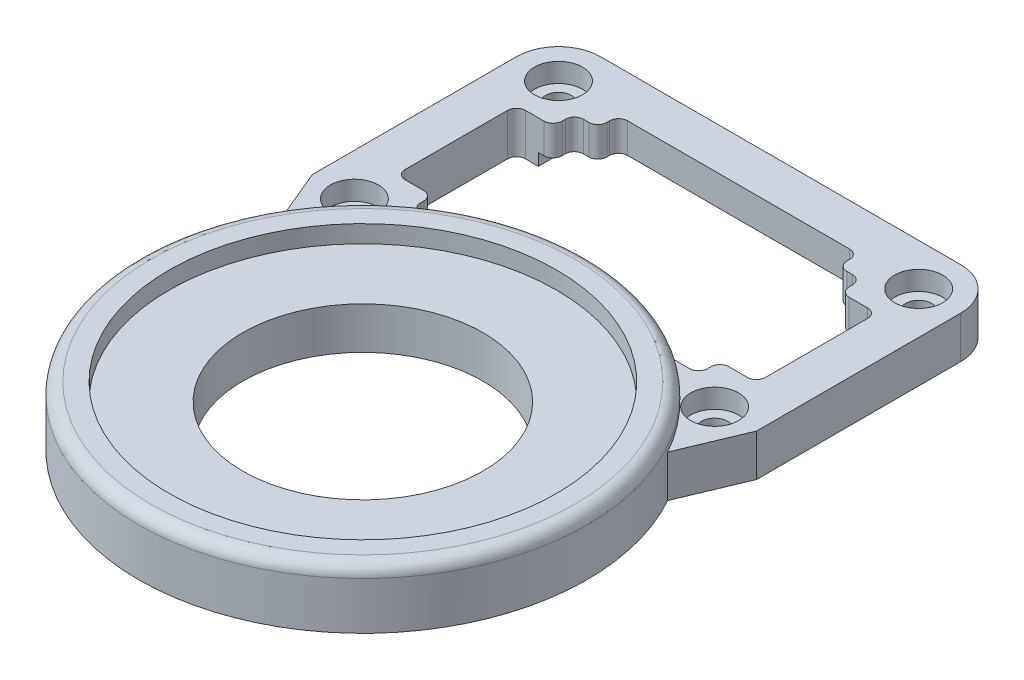
SolidWorks part; units mm, degrees
material "Esun Hard Tough Resin"
ref_plane "Front Plane" through (0, 0, 0) normal (0, 0, 1) x (1, 0, 0)
ref_plane "Top Plane" through (0, 0, 0) normal (0, 1, 0) x (1, 0, 0)
ref_plane "Right Plane" through (0, 0, 0) normal (1, 0, 0) x (0, 0, -1)
sketch "Sketch1" plane through (0, 0, 0) normal (0, 1, 0) x (1, 0, 0)
  line L0 (-18.5013, 8.509) -> (-18.5013, -8.491)
  line L1 (-15.0013, 12.009) -> (14.9987, 12.009)
  line L2 (18.4987, 8.509) -> (18.4987, -8.491)
  line L3 (-18.5013, -8.491) -> (-15.0013, -16.8627)
  line L11 (18.4987, -8.491) -> (15.0013, -16.8627)
  line L13 (-11.9562, -6.7835) -> (11.9562, -6.7835)
  line L14 (-11.9562, -6.7835) -> (-11.9562, -5.009)
  line L15 (-11.9562, 6.7835) -> (-9.9987, 6.7835)
  line L16 (11.9562, -6.7835) -> (11.9562, -5.009)
  line L17 (-11.9562, -6.7835) -> (11.9562, 6.7835) construction
  line L18 (-11.9562, 6.7835) -> (11.9562, -6.7835) construction
  line L19 (14.9987, -8.491) -> (-15.0013, 8.509) construction
  line L20 (14.9987, 8.509) -> (-15.0013, -8.491) construction
  line L22 (-11.9562, 5.009) -> (-15.0013, 5.009)
  line L24 (-11.9562, -5.009) -> (-15.0013, -5.009)
  line L25 (-15.0013, 5.009) -> (-15.0013, -5.009)
  line L32 (-11.9562, 5.009) -> (-11.9562, 6.7835)
  line L33 (0, -1.9432) -> (0, 2.309) construction
  line L36 (15.0013, 5.009) -> (15.0013, -5.009)
  line L37 (11.9562, -5.009) -> (15.0013, -5.009)
  line L38 (11.9562, 5.009) -> (15.0013, 5.009)
  line L39 (11.9562, 5.009) -> (11.9562, 6.7835)
  line L40 (9.9987, 6.7835) -> (9.9987, 8.509)
  line L41 (9.9987, 8.509) -> (-9.9987, 8.509)
  line L42 (-9.9987, 8.509) -> (-9.9987, 6.7835)
  line L43 (9.9987, 6.7835) -> (11.9562, 6.7835)
  circle A31 centre (0, -22.7877) radius 10
  circle A33 centre (-15.0013, 8.509) radius 1.1
  circle A34 centre (-15.0013, -8.491) radius 1.1
  circle A35 centre (14.9987, 8.509) radius 1.1
  circle A36 centre (14.9987, -8.491) radius 1.1
  circle A37 centre (-15.0013, 8.509) radius 1.1 construction
  circle A39 centre (14.9987, 8.509) radius 1.1 construction
  circle A40 centre (14.9987, -8.491) radius 1.1 construction
  circle A41 centre (-15.0013, -8.491) radius 1.1 construction
  arc A46 (-15.0013, 12.009) -> (-18.5013, 8.509) centre (-15.0013, 8.509) ccw
  arc A47 (18.4987, 8.509) -> (14.9987, 12.009) centre (14.9987, 8.509) ccw
  arc A52 (-15.0013, -16.8627) -> (15.0013, -16.8627) centre (0, -22.7877) ccw
  point P24 (0, 0)
  point P37 (-15.0013, 0)
  point P49 (0, 8.509)
  dimension "D3" = 3.5
  dimension "D6" = 14.2967
  dimension "D1" = 7
  dimension "D2" = 3.5
  dimension "D8" = 32.258
  dimension "D5" = 20
  dimension "D4" = 5
extrude "Boss-Extrude1" add sketch "Sketch1" along normal blind 3.5 contours A47 A46 | L3 L11 L2 A47 L1 A46 L0 A33 A34 A35 A36 region at (-0.0013, 0, 12.6874)
sketch "Sketch6" plane through (0, 3.5, 0) normal (0, 1, 0) x (1, 0, 0)
  circle A0 centre (0, -22.7877) radius 16.129
  circle A1 centre (0, -22.7877) radius 18.669
  circle A4 centre (0, -22.7877) radius 10 construction
  line M18 (-18.5013, -8.491) -> (-15.0013, -16.8627)
  line M20 (15.0013, -16.8627) -> (18.4987, -8.491)
  line M32 (11.9562, -6.7835) -> (-11.9562, -6.7835)
  dimension "D1" = 32.258
  dimension "D2" = 2.54
extrude "Boss-Extrude2" add sketch "Sketch6" against normal up to surface (3.5 mm away) contours A1 A0 M18 M20 | A1 A0 | A1 | A1 A0 | A0 M32 region at (16.3015, 3.5, 19.6851) region at (0, 3.5, 6.7335) region at (0, 3.5, 5.7008) up to face at (0, 0, -1.9116)
sketch "Sketch8" plane through (0, 3.5, 0) normal (0, 1, 0) x (1, 0, 0)
  circle A3 centre (0, -22.7877) radius 18.669
  circle A4 centre (0, -22.7877) radius 18.669
  circle A5 centre (0, -22.7877) radius 16.129
  circle A6 centre (0, -22.7877) radius 16.129
  dimension "D2" = 0
  dimension "D3" = 0
extrude "Boss-Extrude4" add sketch "Sketch8" along normal blind 1.453 contours A4 A6 region at (-18.141, 3.5, 22.7877)
sketch "Sketch9" plane through (0, 0, -12.009) normal (0, 0, -1) x (-1, 0, 0)
  line L1 (-13.1757, 1) -> (13.1757, 1)
  line L2 (-13.1757, 1) -> (-13.1757, 0)
  line L3 (-13.1757, 0) -> (13.1757, 0)
  line L4 (13.1757, 1) -> (13.1757, 0)
  line L5 (-13.1757, 1) -> (13.1757, 0) construction
  line L6 (-13.1757, 0) -> (13.1757, 1) construction
  line L8 (15.0013, 0) -> (-14.9987, 0) construction
  point P0 (0, 0.5)
  dimension "D1" = 0.5
  dimension "D2" = 26.3513
extrude "Cut-Extrude1" cut sketch "Sketch9" against normal blind 23.2
hole_wizard "CBORE for M2 Hex Head Machine Screw1" positions "Sketch12" profile "Sketch11" counterbore size "M2" standard "ANSI Metric" end condition up to next
sketch "Sketch12" plane through (0, 3.5, 0) normal (0, 1, 0) x (1, 0, 0)
  point P0 (-15.0013, 8.509)
  point P3 (14.9987, 8.509)
  point P6 (14.9987, -8.491)
  point P9 (-15.0013, -8.491)
sketch "Sketch11" plane through (-15.0013, 3.5, -8.509) normal (1, 0, 0) x (0, 0, 1)
  line L0 (0, 0) -> (0, 3.5)
  line L1 (0, 3.5) -> (1.05, 3.5)
  line L3 (1.05, 3.5) -> (1.05, 1.6)
  line L4 (1.05, 1.6) -> (2, 1.6)
  line L5 (2, 1.6) -> (2, 0)
  line L7 (2, 0) -> (0, 0)
  line L11 (0, -6.35) -> (0, 107.95) construction
  dimension "Thru Hole Dia." = 2.1
  dimension "Thru Hole Depth" = 3.5
  dimension "C'Bore Dia." = 4
  dimension "C'Bore Depth" = 1.6
fillet "Fillet1" radius 0.75 16 edges at (9.9987, 2.25, -6.7835) (11.9562, 2.25, -5.009) (11.9562, 2.25, 5.009) (-9.9987, 2.25, -6.7835) (-11.9562, 2.25, -5.009) (-11.9562, 2.25, 5.009) (-15.0013, 1.75, 5.009) (-11.9562, 2.25, 6.7835) (11.9562, 2.25, 6.7835) (15.0013, 1.75, 5.009) (15.0013, 1.75, -5.009) (11.9562, 2.25, -6.7835) (9.9987, 2.25, -8.509) (-9.9987, 2.25, -8.509) (-11.9562, 2.25, -6.7835) (-15.0013, 1.75, -5.009)
fillet "Fillet2" radius 1 1 edges at (0, 4.953, 41.4567)
